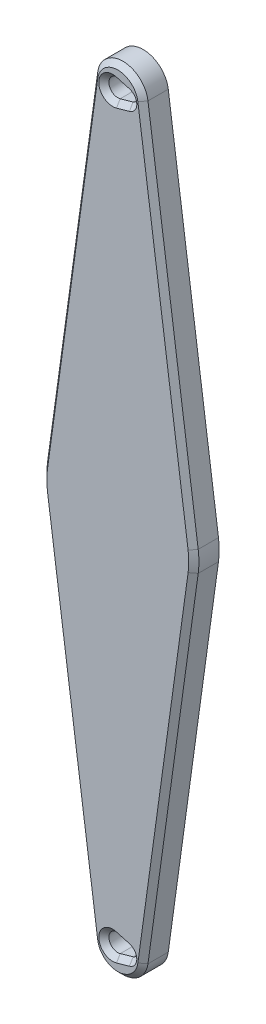
SolidWorks part; units mm, degrees
ref_plane "Front Plane" through (0, 0, 0) normal (0, 0, 1) x (1, 0, 0)
ref_plane "Top Plane" through (0, 0, 0) normal (0, 1, 0) x (1, 0, 0)
ref_plane "Right Plane" through (0, 0, 0) normal (1, 0, 0) x (0, 0, -1)
sketch "Sketch1" plane through (0, 0, 0) normal (0, 0, 1) x (1, 0, 0)
  line L1 (191, 68) -> (85, 68)
  line L2 (85, 68) -> (85, 141) construction
  line L3 (89.9529, 141.6849) -> (99.8586, 70.0548)
  line L8 (0, 136) -> (0, 0)
  line L9 (0, 0) -> (191, 0)
  line L10 (191, 0) -> (191, 136)
  line L11 (191, 136) -> (0, 136)
  line L12 (80.0471, 141.6849) -> (70.1414, 70.0548)
  line L13 (89.9529, -5.6849) -> (99.8586, 65.9452)
  line L14 (80.0471, -5.6849) -> (70.1414, 65.9452)
  circle A0 centre (85, 68) radius 15
  circle A1 centre (85, 141) radius 5
  circle A2 centre (85, -5) radius 5
  dimension "D2" = 30
  dimension "D4" = 10
  dimension "D3" = 5
extrude "Boss-Extrude1" add sketch "Sketch1" along normal blind 5 contours L2 A0 L3 L11 | A0 L2 L11 L12 | A1 | A1 L11 L3 | A1 L12 L11 | L1 L2 A0 | L2 L1 A0 | A0 L14 L9 L13 | L14 A2 L9 | L9 A2 L13 | A2 region at (82.8779, 65.8779, 0) region at (91.3662, 74.3662, 0) region at (90.3088, 104.3689, 0) region at (85, 31.6311, 0) region at (89.2502, -1.2971, 0) region at (89.2502, 137.2971, 0) region at (79.6912, 104.3689, 0) region at (80.7498, -1.2971, 0) region at (85, -5, 0) region at (89.8471, 141.3336, 0) region at (80.7498, 137.2971, 0)
chamfer "Chamfer1" distance 1 angle 45 8 edges at (75.0943, 30.1301, 5) (70, 68, 5) (75.0943, 105.8699, 5) (85, 146, 5) (94.9057, 105.8699, 5) (100, 68, 5) (94.9057, 30.1301, 5) (85, -10, 5)
sketch "Sketch6" plane through (0, 0, 5) normal (0, 0, 1) x (1, 0, 0)
  line L0 (85, 141) -> (84, 141) construction
  line L1 (85, 141) -> (86.75, 141) construction
  line L2 (84.4773, 139.3163) -> (87.0227, 140.0379)
  line L3 (84.4773, 142.6837) -> (87.0227, 141.9621)
  circle A0 centre (84, 141) radius 1.75
  circle A1 centre (86.75, 141) radius 1
  dimension "D1" = 1
  dimension "D2" = 3.5
  dimension "D4" = 2
  dimension "D3" = 1.75
extrude "Cut-Extrude2" cut sketch "Sketch6" against normal up to next contours A1 L3 A0 L2 | A1 | A0 | A1 A0 L2 region at (85.7876, 139.9859, 5) region at (84, 141, 5) region at (86.75, 141, 5) region at (85.7876, 142.0141, 5)
chamfer "Chamfer3" distance 1 angle 45 8 edges at (85.75, 139.6771, 0) (87.75, 141, 0) (82.25, 141, 0) (85.75, 142.3229, 0) (87.75, 141, 5) (85.75, 139.6771, 5) (82.25, 141, 5) (85.75, 142.3229, 5)
sketch "Sketch7" plane through (0, 0, 5) normal (0, 0, 1) x (1, 0, 0)
  line L1 (190.9983, 68.6016) -> (85, 68) construction
  line L2 (190.9983, 68.6016) -> (85, 68) construction
ref_axis "Axis2" through (85, 68, 5) along (0, 0, -1)
sketch "Sketch8" plane through (0, 0, 0) normal (0, 0, -1) x (-1, 0, 0)
  line L0 (-100, 68) -> (-70, 68) construction
  arc A0 (-99.8586, 70.0548) -> (-99.8586, 65.9452) centre (-85, 68) ccw construction
  arc A1 (-70.1414, 65.9452) -> (-70.1414, 70.0548) centre (-85, 68) ccw construction
ref_axis "Axis3" through (100, 68, 0) along (-1, 0, 0)
ref_plane "Plane3" through (0, 68, 0) normal (0, -1, 0) x (-1, 0, 0)
mirror "Mirror2" about plane through (0, 68, 0) normal (0, -1, 0) of "Cut-Extrude2", "Chamfer3"
